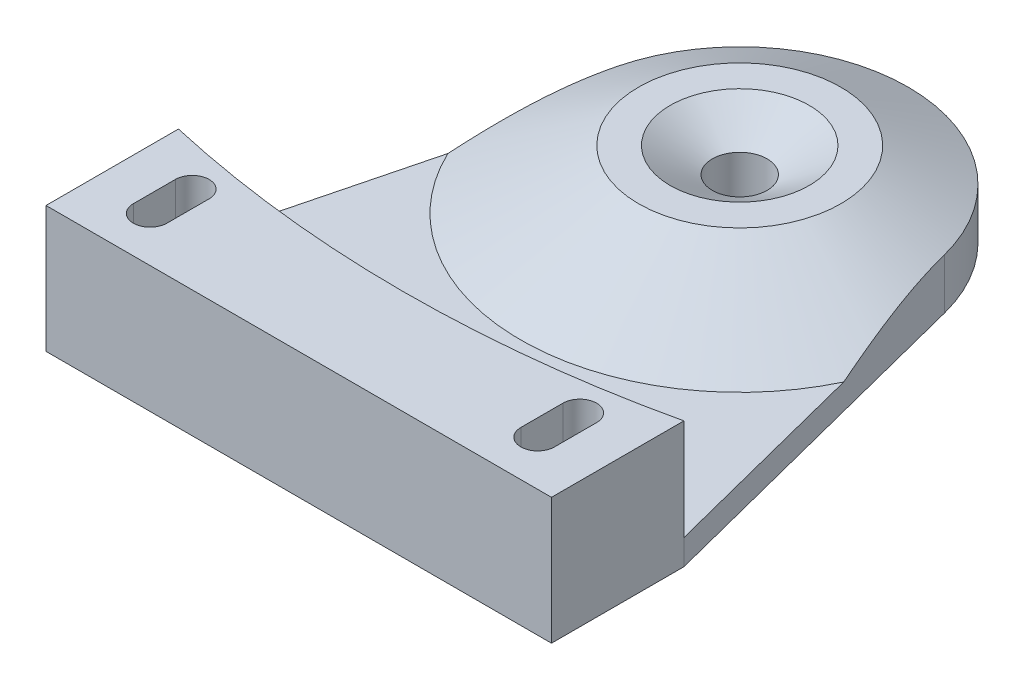
SolidWorks part; units mm, degrees
ref_plane "Front Plane" through (0, 0, 0) normal (0, 0, 1) x (1, 0, 0)
ref_plane "Top Plane" through (0, 0, 0) normal (0, 1, 0) x (1, 0, 0)
ref_plane "Right Plane" through (0, 0, 0) normal (1, 0, 0) x (0, 0, -1)
sketch "Sketch1" plane through (0, 0, 0) normal (0, 1, 0) x (1, 0, 0)
  line L0 (-30, -18) -> (30, -18) construction
  line L1 (-30, 10) -> (-22.5, 10) construction
  line L2 (-46.46, 5.4904) -> (-53.96, -7.5) construction
  line L3 (-30, -10) -> (-22.5, -10) construction
  line L4 (30, 10) -> (30, 2.5) construction
  line L5 (0, 0) -> (0, -75.5561) construction
  line L6 (38.6603, -23) -> (51.362, -45) construction
  line L7 (55.7735, -52.641) -> (58.3716, -51.141) construction
  line L8 (59.1036, -48.409) -> (41.8357, -18.5) construction
  line L9 (43.1036, -13.7679) -> (55.6921, -6.5) construction
  line L10 (56.4241, -3.7679) -> (51.362, 5) construction
  line L11 (25.3812, 20) -> (-25.3812, 20) construction
  line L12 (43.5677, -13.5) -> (36.0677, -0.5096) construction
  line L13 (36.0677, -0.5096) -> (46.46, 5.4904) construction
  line L14 (46.46, 5.4904) -> (53.96, -7.5) construction
  line L15 (-36.0677, -0.5096) -> (-46.46, 5.4904) construction
  line L16 (-43.5677, -13.5) -> (-36.0677, -0.5096) construction
  line L17 (-56.4241, -3.7679) -> (-51.362, 5) construction
  line L18 (-43.1036, -13.7679) -> (-55.6921, -6.5) construction
  line L19 (-59.1036, -48.409) -> (-41.8357, -18.5) construction
  line L20 (-55.7735, -52.641) -> (-58.3716, -51.141) construction
  line L21 (-38.6603, -23) -> (-51.362, -45) construction
  line L22 (-30, 10) -> (-30, 2.5) construction
  line L23 (30, 2.5) -> (25, 2.5) construction
  line L24 (25, 2.5) -> (25, -2.5) construction
  line L25 (25, -2.5) -> (30, -2.5) construction
  line L26 (30, -2.5) -> (30, -10) construction
  line L27 (22.5, -10) -> (22.5, -5) construction
  line L28 (22.5, -5) -> (17.5, -5) construction
  line L29 (17.5, -5) -> (17.5, -10) construction
  line L30 (22.5, -10) -> (30, -10) construction
  line L31 (17.5, 10) -> (17.5, 9) construction
  line L32 (17.5, 9) -> (22.5, 9) construction
  line L33 (22.5, 9) -> (22.5, 10) construction
  line L34 (22.5, 10) -> (30, 10) construction
  line L35 (2.5, -10) -> (2.5, -5) construction
  line L36 (2.5, -5) -> (-2.5, -5) construction
  line L37 (-2.5, -5) -> (-2.5, -10) construction
  line L38 (-2.5, 10) -> (-2.5, 9) construction
  line L39 (-2.5, 9) -> (2.5, 9) construction
  line L40 (2.5, 9) -> (2.5, 10) construction
  line L41 (-17.5, -10) -> (-17.5, -5) construction
  line L42 (-17.5, -5) -> (-22.5, -5) construction
  line L43 (-22.5, -5) -> (-22.5, -10) construction
  line L44 (-22.5, 10) -> (-22.5, 9) construction
  line L45 (-22.5, 9) -> (-17.5, 9) construction
  line L46 (-17.5, 9) -> (-17.5, 10) construction
  line L47 (-17.5, 10) -> (-2.5, 10) construction
  line L48 (-17.5, -10) -> (-2.5, -10) construction
  line L49 (2.5, -10) -> (17.5, -10) construction
  line L50 (2.5, 10) -> (17.5, 10) construction
  line L51 (-25, -2.5) -> (-30, -2.5) construction
  line L52 (-25, 2.5) -> (-25, -2.5) construction
  line L53 (-30, 2.5) -> (-25, 2.5) construction
  line L54 (-30, -2.5) -> (-30, -10) construction
  line L55 (-54.8261, -52) -> (54.8261, -52) construction
  line L56 (-49.6299, -48) -> (49.6299, -48) construction
  line L57 (-55.6921, -52.5) -> (-55.7735, -52.641) construction
  line L58 (55.6921, -52.5) -> (55.7735, -52.641) construction
  line L59 (207.8868, -326.1089) -> (177.8868, -378.0704) construction
  line L60 (232.1355, -340.1089) -> (228.3855, -346.6041) construction
  line L61 (214.815, -330.1089) -> (211.065, -336.6041) construction
  line L62 (202.1355, -392.0704) -> (195.6403, -388.3204) construction
  line L63 (169.2265, -383.0704) -> (143.8231, -383.0704) construction
  line L64 (135, -383.0704) -> (135, -386.0704) construction
  line L65 (137, -388.0704) -> (171.5359, -388.0704) construction
  line L66 (175, -391.5345) -> (175, -406.0704) construction
  line L67 (177, -408.0704) -> (187.1244, -408.0704) construction
  line L68 (213.1051, -393.0704) -> (238.4863, -349.1089) construction
  line L69 (233.4241, -310.3409) -> (238.4863, -319.1089) construction
  line L70 (218.1036, -316.8768) -> (230.6921, -309.6089) construction
  line L71 (196.1036, -285.6999) -> (213.3716, -315.6089) construction
  line L72 (190.7735, -286.4679) -> (193.3716, -284.9679) construction
  line L73 (207.8868, -316.1089) -> (195.185, -294.1089) construction
  line L74 (232.1355, -340.1089) -> (225.6403, -336.3589) construction
  line L75 (195.6403, -388.3204) -> (198.1403, -383.9903) construction
  line L76 (198.1403, -383.9903) -> (193.8101, -381.4903) construction
  line L77 (193.8101, -381.4903) -> (191.3101, -385.8204) construction
  line L78 (191.3101, -385.8204) -> (184.815, -382.0704) construction
  line L79 (188.565, -375.5752) -> (192.8951, -378.0752) construction
  line L80 (192.8951, -378.0752) -> (195.3951, -373.7451) construction
  line L81 (195.3951, -373.7451) -> (191.065, -371.2451) construction
  line L82 (188.565, -375.5752) -> (184.815, -382.0704) construction
  line L83 (208.3855, -381.2451) -> (207.5194, -380.7451) construction
  line L84 (207.5194, -380.7451) -> (205.0194, -385.0752) construction
  line L85 (205.0194, -385.0752) -> (205.8855, -385.5752) construction
  line L86 (205.8855, -385.5752) -> (202.1355, -392.0704) construction
  line L87 (198.565, -358.2547) -> (202.8951, -360.7547) construction
  line L88 (202.8951, -360.7547) -> (205.3951, -356.4246) construction
  line L89 (205.3951, -356.4246) -> (201.065, -353.9246) construction
  line L90 (218.3855, -363.9246) -> (217.5194, -363.4246) construction
  line L91 (217.5194, -363.4246) -> (215.0194, -367.7547) construction
  line L92 (215.0194, -367.7547) -> (215.8855, -368.2547) construction
  line L93 (208.565, -340.9342) -> (212.8951, -343.4342) construction
  line L94 (212.8951, -343.4342) -> (215.3951, -339.1041) construction
  line L95 (215.3951, -339.1041) -> (211.065, -336.6041) construction
  line L96 (228.3855, -346.6041) -> (227.5194, -346.1041) construction
  line L97 (227.5194, -346.1041) -> (225.0194, -350.4342) construction
  line L98 (225.0194, -350.4342) -> (225.8855, -350.9342) construction
  line L99 (225.8855, -350.9342) -> (218.3855, -363.9246) construction
  line L100 (208.565, -340.9342) -> (201.065, -353.9246) construction
  line L101 (198.565, -358.2547) -> (191.065, -371.2451) construction
  line L102 (215.8855, -368.2547) -> (208.3855, -381.2451) construction
  line L103 (218.8101, -338.189) -> (221.3101, -333.8589) construction
  line L104 (223.1403, -340.689) -> (218.8101, -338.189) construction
  line L105 (225.6403, -336.3589) -> (223.1403, -340.689) construction
  line L106 (221.3101, -333.8589) -> (214.815, -330.1089) construction
  line L107 (190.8549, -287.6089) -> (136.0289, -382.5704) construction
  line L108 (191.7209, -294.1089) -> (142.091, -380.0704) construction
  line L109 (190.8549, -286.6089) -> (190.7735, -286.4679) construction
  line L110 (135.1628, -383.0704) -> (135, -383.0704) construction
  line L111 (236.46, -323.5993) -> (228.96, -310.6089) construction
  line L112 (175, -392.0704) -> (190, -392.0704) construction
  line L113 (190, -392.0704) -> (190, -404.0704) construction
  line L114 (190, -404.0704) -> (175, -404.0704) construction
  line L115 (226.0677, -329.5993) -> (236.46, -323.5993) construction
  line L116 (218.5677, -316.6089) -> (226.0677, -329.5993) construction
  line L117 (-177.8868, -378.0704) -> (-207.8868, -326.1089) construction
  line L118 (-202.1355, -392.0704) -> (-205.8855, -385.5752) construction
  line L119 (-184.815, -382.0704) -> (-188.565, -375.5752) construction
  line L120 (-232.1355, -340.1089) -> (-225.6403, -336.3589) construction
  line L121 (-207.8868, -316.1089) -> (-195.185, -294.1089) construction
  line L122 (-190.7735, -286.4679) -> (-193.3716, -284.9679) construction
  line L123 (-196.1036, -285.6999) -> (-213.3716, -315.6089) construction
  line L124 (-218.1036, -316.8768) -> (-230.6921, -309.6089) construction
  line L125 (-233.4241, -310.3409) -> (-238.4863, -319.1089) construction
  line L126 (-238.4863, -349.1089) -> (-213.1051, -393.0704) construction
  line L127 (-177, -408.0704) -> (-187.1244, -408.0704) construction
  line L128 (-175, -391.5345) -> (-175, -406.0704) construction
  line L129 (-137, -388.0704) -> (-171.5359, -388.0704) construction
  line L130 (-135, -383.0704) -> (-135, -386.0704) construction
  line L131 (-169.2265, -383.0704) -> (-143.8231, -383.0704) construction
  line L132 (-202.1355, -392.0704) -> (-195.6403, -388.3204) construction
  line L133 (-225.6403, -336.3589) -> (-223.1403, -340.689) construction
  line L134 (-223.1403, -340.689) -> (-218.8101, -338.189) construction
  line L135 (-218.8101, -338.189) -> (-221.3101, -333.8589) construction
  line L136 (-221.3101, -333.8589) -> (-214.815, -330.1089) construction
  line L137 (-211.065, -336.6041) -> (-215.3951, -339.1041) construction
  line L138 (-215.3951, -339.1041) -> (-212.8951, -343.4342) construction
  line L139 (-212.8951, -343.4342) -> (-208.565, -340.9342) construction
  line L140 (-211.065, -336.6041) -> (-214.815, -330.1089) construction
  line L141 (-225.8855, -350.9342) -> (-225.0194, -350.4342) construction
  line L142 (-225.0194, -350.4342) -> (-227.5194, -346.1041) construction
  line L143 (-227.5194, -346.1041) -> (-228.3855, -346.6041) construction
  line L144 (-228.3855, -346.6041) -> (-232.1355, -340.1089) construction
  line L145 (-201.065, -353.9246) -> (-205.3951, -356.4246) construction
  line L146 (-205.3951, -356.4246) -> (-202.8951, -360.7547) construction
  line L147 (-202.8951, -360.7547) -> (-198.565, -358.2547) construction
  line L148 (-215.8855, -368.2547) -> (-215.0194, -367.7547) construction
  line L149 (-215.0194, -367.7547) -> (-217.5194, -363.4246) construction
  line L150 (-217.5194, -363.4246) -> (-218.3855, -363.9246) construction
  line L151 (-191.065, -371.2451) -> (-195.3951, -373.7451) construction
  line L152 (-195.3951, -373.7451) -> (-192.8951, -378.0752) construction
  line L153 (-192.8951, -378.0752) -> (-188.565, -375.5752) construction
  line L154 (-205.8855, -385.5752) -> (-205.0194, -385.0752) construction
  line L155 (-205.0194, -385.0752) -> (-207.5194, -380.7451) construction
  line L156 (-207.5194, -380.7451) -> (-208.3855, -381.2451) construction
  line L157 (-208.3855, -381.2451) -> (-215.8855, -368.2547) construction
  line L158 (-191.065, -371.2451) -> (-198.565, -358.2547) construction
  line L159 (-201.065, -353.9246) -> (-208.565, -340.9342) construction
  line L160 (-218.3855, -363.9246) -> (-225.8855, -350.9342) construction
  line L161 (-193.8101, -381.4903) -> (-191.3101, -385.8204) construction
  line L162 (-198.1403, -383.9903) -> (-193.8101, -381.4903) construction
  line L163 (-195.6403, -388.3204) -> (-198.1403, -383.9903) construction
  line L164 (-191.3101, -385.8204) -> (-184.815, -382.0704) construction
  line L165 (-136.0289, -382.5704) -> (-190.8549, -287.6089) construction
  line L166 (-142.091, -380.0704) -> (-191.7209, -294.1089) construction
  line L167 (-135.1628, -383.0704) -> (-135, -383.0704) construction
  line L168 (-190.8549, -286.6089) -> (-190.7735, -286.4679) construction
  line L169 (-190, -404.0704) -> (-175, -404.0704) construction
  line L170 (-218.5677, -316.6089) -> (-226.0677, -329.5993) construction
  line L171 (-226.0677, -329.5993) -> (-236.46, -323.5993) construction
  line L172 (-236.46, -323.5993) -> (-228.96, -310.6089) construction
  line L173 (-190, -392.0704) -> (-190, -404.0704) construction
  line L174 (-175, -392.0704) -> (-190, -392.0704) construction
  line L175 (-132.8534, -388.0704) -> (132.8534, -388.0704) construction
  line L176 (-132.8534, -388.0704) -> (-194.0303, -282.1089) construction
  line L177 (-194.0303, -282.1089) -> (-61.1769, -52) construction
  line L178 (-61.1769, -52) -> (61.1769, -52) construction
  line L179 (61.1769, -52) -> (194.0303, -282.1089) construction
  line L180 (-30, -388.0704) -> (30, -388.0704)
  line L181 (132.8534, -388.0704) -> (194.0303, -282.1089) construction
  line L182 (30, -372.3509) -> (30, -388.0704)
  line L183 (-30, -372.3509) -> (-30, -388.0704)
  line L184 (-21, -382.7107) -> (-21, -377.7107)
  line L185 (-25, -377.7107) -> (-25, -382.7107)
  line L186 (-30, -380.2107) -> (-25, -380.2107) construction
  line L187 (25, -377.7107) -> (25, -382.7107)
  line L188 (21, -382.7107) -> (21, -377.7107)
  circle A0 centre (0, 0) radius 31.6228 construction
  arc A1 (30, -18) -> (38.6603, -23) centre (30, -28) cw construction
  arc A2 (51.362, 5) -> (25.3812, 20) centre (25.3812, -10) ccw construction
  arc A3 (41.1036, -13.7679) -> (40.1036, -17.5) centre (40.1036, -15.5) ccw construction
  arc A4 (58.3716, -51.141) -> (59.1036, -48.409) centre (57.3716, -49.409) ccw construction
  arc A5 (55.6921, -6.5) -> (56.4241, -3.7679) centre (54.6921, -4.7679) ccw construction
  arc A6 (40.1036, -17.5) -> (41.8357, -18.5) centre (40.1036, -19.5) cw construction
  arc A7 (41.1036, -13.7679) -> (43.1036, -13.7679) centre (42.1036, -12.0359) ccw construction
  arc A8 (-41.1036, -13.7679) -> (-43.1036, -13.7679) centre (-42.1036, -12.0359) cw construction
  arc A9 (-40.1036, -17.5) -> (-41.8357, -18.5) centre (-40.1036, -19.5) ccw construction
  arc A10 (-55.6921, -6.5) -> (-56.4241, -3.7679) centre (-54.6921, -4.7679) cw construction
  arc A11 (-58.3716, -51.141) -> (-59.1036, -48.409) centre (-57.3716, -49.409) cw construction
  arc A12 (-41.1036, -13.7679) -> (-40.1036, -17.5) centre (-40.1036, -15.5) cw construction
  arc A13 (-51.362, 5) -> (-25.3812, 20) centre (-25.3812, -10) cw construction
  arc A14 (-30, -18) -> (-38.6603, -23) centre (-30, -28) ccw construction
  arc A15 (55.6921, -52.5) -> (54.8261, -52) centre (54.8261, -53) ccw construction
  arc A16 (-54.8261, -52) -> (-55.6921, -52.5) centre (-54.8261, -53) ccw construction
  arc A17 (49.6299, -48) -> (51.362, -45) centre (49.6299, -46) ccw construction
  arc A18 (-49.6299, -48) -> (-51.362, -45) centre (-49.6299, -46) cw construction
  circle A19 centre (0, -240.7264) radius 147.344 construction
  arc A20 (177.8868, -378.0704) -> (169.2265, -383.0704) centre (169.2265, -373.0704) cw construction
  arc A21 (187.1244, -408.0704) -> (213.1051, -393.0704) centre (187.1244, -378.0704) ccw construction
  arc A22 (176, -389.8025) -> (173.2679, -387.0704) centre (175, -388.0704) ccw construction
  arc A23 (135, -386.0704) -> (137, -388.0704) centre (137, -386.0704) ccw construction
  arc A24 (175, -406.0704) -> (177, -408.0704) centre (177, -406.0704) ccw construction
  arc A25 (173.2679, -387.0704) -> (171.5359, -388.0704) centre (171.5359, -386.0704) cw construction
  arc A26 (176, -389.8025) -> (175, -391.5345) centre (177, -391.5345) ccw construction
  arc A27 (217.1036, -318.6089) -> (218.1036, -316.8768) centre (219.1036, -318.6089) cw construction
  arc A28 (213.3716, -317.6089) -> (213.3716, -315.6089) centre (211.6395, -316.6089) ccw construction
  arc A29 (230.6921, -309.6089) -> (233.4241, -310.3409) centre (231.6921, -311.3409) cw construction
  arc A30 (193.3716, -284.9679) -> (196.1036, -285.6999) centre (194.3716, -286.6999) cw construction
  arc A31 (217.1036, -318.6089) -> (213.3716, -317.6089) centre (215.1036, -318.6089) cw construction
  arc A32 (238.4863, -319.1089) -> (238.4863, -349.1089) centre (212.5056, -334.1089) cw construction
  arc A33 (207.8868, -326.1089) -> (207.8868, -316.1089) centre (199.2265, -321.1089) ccw construction
  arc A34 (135.1628, -383.0704) -> (136.0289, -382.5704) centre (135.1628, -382.0704) ccw construction
  arc A35 (190.8549, -287.6089) -> (190.8549, -286.6089) centre (189.9889, -287.1089) ccw construction
  arc A36 (142.091, -380.0704) -> (143.8231, -383.0704) centre (143.8231, -381.0704) ccw construction
  arc A37 (191.7209, -294.1089) -> (195.185, -294.1089) centre (193.453, -295.1089) cw construction
  arc A38 (-207.8868, -326.1089) -> (-207.8868, -316.1089) centre (-199.2265, -321.1089) cw construction
  arc A39 (-238.4863, -319.1089) -> (-238.4863, -349.1089) centre (-212.5056, -334.1089) ccw construction
  arc A40 (-217.1036, -318.6089) -> (-213.3716, -317.6089) centre (-215.1036, -318.6089) ccw construction
  arc A41 (-193.3716, -284.9679) -> (-196.1036, -285.6999) centre (-194.3716, -286.6999) ccw construction
  arc A42 (-230.6921, -309.6089) -> (-233.4241, -310.3409) centre (-231.6921, -311.3409) ccw construction
  arc A43 (-213.3716, -317.6089) -> (-213.3716, -315.6089) centre (-211.6395, -316.6089) cw construction
  arc A44 (-217.1036, -318.6089) -> (-218.1036, -316.8768) centre (-219.1036, -318.6089) ccw construction
  arc A45 (-176, -389.8025) -> (-175, -391.5345) centre (-177, -391.5345) cw construction
  arc A46 (-173.2679, -387.0704) -> (-171.5359, -388.0704) centre (-171.5359, -386.0704) ccw construction
  arc A47 (-175, -406.0704) -> (-177, -408.0704) centre (-177, -406.0704) cw construction
  arc A48 (-135, -386.0704) -> (-137, -388.0704) centre (-137, -386.0704) cw construction
  arc A49 (-176, -389.8025) -> (-173.2679, -387.0704) centre (-175, -388.0704) cw construction
  arc A50 (-187.1244, -408.0704) -> (-213.1051, -393.0704) centre (-187.1244, -378.0704) cw construction
  arc A51 (-177.8868, -378.0704) -> (-169.2265, -383.0704) centre (-169.2265, -373.0704) ccw construction
  arc A52 (-190.8549, -286.6089) -> (-190.8549, -287.6089) centre (-189.9889, -287.1089) ccw construction
  arc A53 (-136.0289, -382.5704) -> (-135.1628, -383.0704) centre (-135.1628, -382.0704) ccw construction
  arc A54 (-191.7209, -294.1089) -> (-195.185, -294.1089) centre (-193.453, -295.1089) ccw construction
  arc A55 (-142.091, -380.0704) -> (-143.8231, -383.0704) centre (-143.8231, -381.0704) cw construction
  arc A56 (-30, -372.3509) -> (30, -372.3509) centre (0, -240.7264) ccw
  arc A57 (-21, -377.7107) -> (-25, -377.7107) centre (-23, -377.7107) ccw
  arc A58 (-25, -382.7107) -> (-21, -382.7107) centre (-23, -382.7107) ccw
  arc A59 (25, -382.7107) -> (21, -382.7107) centre (23, -382.7107) cw
  arc A60 (21, -377.7107) -> (25, -377.7107) centre (23, -377.7107) cw
  point P7 (-57.4241, -5.5)
  point P9 (0, -18)
  point P22 (35.7735, -18)
  point P27 (0, 10)
  point P30 (60.1036, -50.141)
  point P33 (57.4241, -5.5)
  point P61 (0, 20)
  point P65 (-60.1036, -50.141)
  point P66 (-35.7735, -18)
  point P104 (55.4034, -52)
  point P107 (-55.4034, -52)
  point P120 (232.4241, -308.6089)
  point P122 (192.8868, -352.0897)
  point P137 (217.1355, -366.0897)
  point P169 (225.7957, -371.0897)
  point P173 (195.1036, -283.9679)
  point P174 (210.7735, -321.1089)
  point P222 (-175, -408.0704)
  point P224 (-192.8868, -352.0897)
  point P239 (-217.1355, -366.0897)
  point P271 (-225.7957, -371.0897)
  point P275 (-135, -388.0704)
  point P276 (-175, -383.0704)
  point P320 (0, -240.7264)
  dimension "D12" = 10
  dimension "D14" = 30
  dimension "D16" = 2
  dimension "D17" = 2
  dimension "D28" = 1
  dimension "D29" = 2
  dimension "D31" = 270
  dimension "D35" = 2
  dimension "D2" = 30
  dimension "D3" = 5
  dimension "D4" = 8
  dimension "D5" = 40
  dimension "D6" = 20
  dimension "D7" = 350
  dimension "D8" = 10
  dimension "D9" = 4
  dimension "D10" = 12
  dimension "D11" = 15
  dimension "D13" = 20
  dimension "D15" = 34
  dimension "D18" = 5
  dimension "D19" = 2.5
  dimension "D20" = 5
  dimension "D21" = 5
  dimension "D22" = 5
  dimension "D23" = 7.5
  dimension "D24" = 1
  dimension "D26" = 20
  dimension "D27" = 4
  dimension "D32" = 60
  dimension "D33" = 30
  dimension "D34" = 5
  dimension "D36" = 5
  dimension "D25" = 3
  dimension "D30" = 3
extrude "Boss-Extrude1" add sketch "Sketch1" along normal blind 15
sketch "Sketch2" plane through (0, 0, 0) normal (0, 1, 0) x (1, 0, 0)
  line L0 (30, -372.3509) -> (19.3775, -330.7755)
  line L1 (-30, -372.3509) -> (-19.3775, -330.7755)
  line L2 (0, -375.7264) -> (0, -335.7264) construction
  arc A0 (19.3775, -330.7755) -> (-19.3775, -330.7755) centre (0, -335.7264) ccw
  arc A1 (-30, -372.3509) -> (30, -372.3509) centre (0, -240.7264) ccw construction
  arc A2 (-30, -372.3509) -> (30, -372.3509) centre (0, -240.7264) ccw
  dimension "D2" = 20
  dimension "D1" = 40
extrude "Boss-Extrude2" add sketch "Sketch2" along normal blind 10
sketch "Sketch3" plane through (0, 10, 0) normal (0, 1, 0) x (1, 0, 0)
  circle A0 centre (0, -335.7264) radius 3.25
  arc A1 (19.3775, -330.7755) -> (-19.3775, -330.7755) centre (0, -335.7264) ccw construction
  dimension "D1" = 6.5
extrude "Cut-Extrude1" cut sketch "Sketch3" against normal offset from surface (9 mm away) 1 contours A0 up to face at (-23, 0, 380.2107)
sketch "Sketch4" plane through (0, 10, 0) normal (0, 1, 0) x (1, 0, 0)
  line L0 (30, -372.3509) -> (19.3775, -330.7755)
  line L1 (-30, -372.3509) -> (-19.3775, -330.7755)
  circle A0 centre (0, -335.7264) radius 6
  arc A1 (19.3775, -330.7755) -> (-19.3775, -330.7755) centre (0, -335.7264) ccw
  arc A2 (-30, -372.3509) -> (30, -372.3509) centre (0, -240.7264) ccw
  arc A3 (-30, -372.3509) -> (30, -372.3509) centre (0, -240.7264) ccw construction
  dimension "D1" = 12
extrude "Cut-Extrude2" cut sketch "Sketch4" against normal offset from surface (7 mm away) 3 up to face at (-23, 0, 380.2107)
chamfer "Chamfer1" distance 10 distance2 20 1 edges at (0, 3, 341.7264) first distance on face at (0, 3, 341.7264)
chamfer "Chamfer2" distance 5 distance2 3 1 edges at (0, 10, 338.9764) first distance on face at (0, 10, 347.7264)
